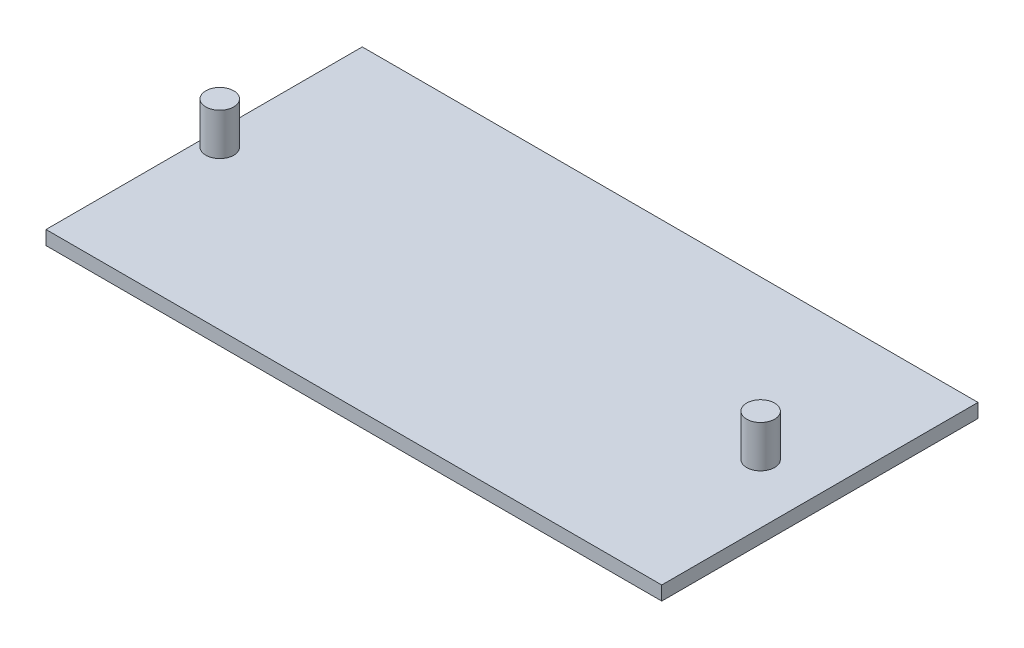
SolidWorks part; units mm, degrees
ref_plane "Front Plane" through (0, 0, 0) normal (0, 0, 1) x (1, 0, 0)
ref_plane "Top Plane" through (0, 0, 0) normal (0, 1, 0) x (1, 0, 0)
ref_plane "Right Plane" through (0, 0, 0) normal (1, 0, 0) x (0, 0, -1)
sketch "Sketch1" plane through (0, 0, 0) normal (0, 1, 0) x (1, 0, 0)
  line L1 (0, 0) -> (139.954, 0)
  line L2 (0, 0) -> (0, 71.882)
  line L3 (0, 71.882) -> (139.954, 71.882)
  line L4 (139.954, 0) -> (139.954, 71.882)
  circle A0 centre (6.35, 35.941) radius 4.191
  circle A1 centre (129.286, 35.941) radius 4.191
  dimension "D4" = 8.382
  dimension "D6" = 8.382
  dimension "D1" = 71.882
  dimension "D2" = 139.954
  dimension "D3" = 6.35
  dimension "D5" = 35.941
  dimension "D7" = 122.936
extrude "Boss-Extrude1" add sketch "Sketch1" against normal blind 3.175
sketch "Sketch2" plane through (0, -3.175, 0) normal (0, -1, 0) x (1, 0, 0)
  circle A0 centre (6.35, -35.941) radius 3.175
  circle A1 centre (129.286, -35.941) radius 3.175
  dimension "D1" = 6.35
  dimension "D2" = 6.35
extrude "Boss-Extrude4" add sketch "Sketch2" against normal blind 12.7
extrude "Boss-Extrude5" add sketch "Sketch1<7>" against normal blind 3.175 contours A1
sketch "Sketch1<7>" plane through (0, 0, 0) normal (0, 1, 0) x (1, 0, 0) same geometry as "Sketch1"
sketch "Sketch14" plane through (0, -3.175, 0) normal (0, -1, 0) x (1, 0, 0)
  circle A0 centre (6.35, -35.941) radius 4.191
  dimension "D1" = 8.382
extrude "Boss-Extrude6" add sketch "Sketch14" against normal blind 3.175
sketch "Sketch15" plane through (0, 0, 0) normal (-1, 0, 0) x (0, 0, 1)
  line L1 (-71.882, -3.175) -> (0, -3.175)
  line L2 (-71.882, -3.175) -> (-71.882, 0)
  line L3 (-71.882, 0) -> (0, 0)
  line L4 (0, -3.175) -> (0, 0)
extrude "Cut-Extrude1" cut sketch "Sketch15" against normal blind 2.794
sketch "Sketch16" plane through (139.954, 0, 0) normal (1, 0, 0) x (0, 0, -1)
  line L1 (0, -3.175) -> (71.882, -3.175)
  line L2 (0, -3.175) -> (0, 0)
  line L3 (0, 0) -> (71.882, 0)
  line L4 (71.882, -3.175) -> (71.882, 0)
extrude "Boss-Extrude7" add sketch "Sketch16" along normal blind 2.794
